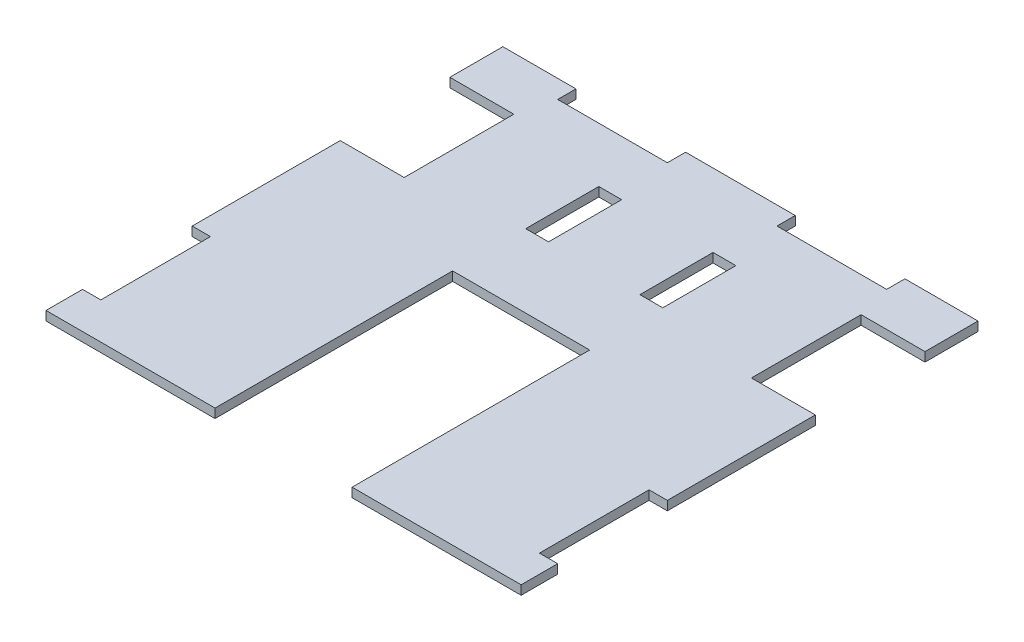
SolidWorks part; units mm, degrees
material "7050-T73510"
ref_plane "Front Plane" through (0, 0, 0) normal (0, 0, 1) x (1, 0, 0)
ref_plane "Top Plane" through (0, 0, 0) normal (0, 1, 0) x (1, 0, 0)
ref_plane "Right Plane" through (0, 0, 0) normal (1, 0, 0) x (0, 0, -1)
sketch "Sketch1" plane through (0, 0, 0) normal (0, 1, 0) x (1, 0, 0)
  line L0 (0, -55) -> (0, 55) construction
  line L1 (-165.1, -76.2) -> (165.1, -76.2)
  line L2 (-165.1, -76.2) -> (-165.1, 76.2)
  line L3 (-165.1, 76.2) -> (165.1, 76.2)
  line L4 (165.1, -76.2) -> (165.1, 76.2)
  line L5 (-165.1, -76.2) -> (165.1, 76.2) construction
  line L6 (-165.1, 76.2) -> (165.1, -76.2) construction
  line L7 (-165.1, -76.2) -> (-31.75, -76.2)
  line L8 (-165.1, -76.2) -> (-165.1, -241.3)
  line L9 (-165.1, -241.3) -> (-31.75, -241.3)
  line L10 (-31.75, -76.2) -> (-31.75, -241.3)
  line L11 (31.75, -76.2) -> (31.75, -241.3)
  line L12 (165.1, -241.3) -> (31.75, -241.3)
  line L13 (165.1, -76.2) -> (165.1, -241.3)
  line L14 (165.1, -76.2) -> (31.75, -76.2)
  line L15 (-47.625, -76.2) -> (-47.625, -241.3)
  line L16 (47.625, -76.2) -> (47.625, -241.3)
  point P0 (0, 0)
  dimension "D1" = 330.2
  dimension "D2" = 152.4
  dimension "D3" = 317.5
  dimension "D4" = 63.5
  dimension "D5" = 15.875
extrude "Boss-Extrude1" add sketch "Sketch1" along normal blind 6.35 contours L15 L1 L8 L9 | L14 L16 L12 L13 | L1 L7 L14 L4 L3 L2 region at (0, 0, 0) region at (-106.3625, 0, 158.75) region at (106.3625, 0, 158.75)
sketch "Sketch2" plane through (0, 6.35, 0) normal (0, 1, 0) x (1, 0, 0)
  line L0 (165.1, -241.3) -> (165.1, 76.2) construction
  line L1 (165.1, 39.37) -> (120.65, 39.37)
  line L2 (165.1, 39.37) -> (165.1, -36.83)
  line L3 (165.1, -36.83) -> (120.65, -36.83)
  line L4 (120.65, 39.37) -> (120.65, -36.83)
  line L5 (-165.1, 76.2) -> (165.1, 76.2) construction
  line L6 (165.1, -139.7) -> (152.4, -139.7)
  line L7 (165.1, -139.7) -> (165.1, -215.9)
  line L8 (165.1, -215.9) -> (152.4, -215.9)
  line L9 (152.4, -139.7) -> (152.4, -215.9)
  line L10 (0, -55) -> (0, 55) construction
  line L11 (-165.1, -215.9) -> (-152.4, -215.9)
  line L12 (-152.4, -139.7) -> (-152.4, -215.9)
  line L13 (-165.1, -139.7) -> (-152.4, -139.7)
  line L14 (-165.1, -139.7) -> (-165.1, -215.9)
  line L15 (-165.1, -36.83) -> (-120.65, -36.83)
  line L16 (-120.65, 39.37) -> (-120.65, -36.83)
  line L17 (-165.1, 39.37) -> (-120.65, 39.37)
  line L18 (-165.1, 39.37) -> (-165.1, -36.83)
  line L19 (-114.3, 63.5) -> (-38.1, 63.5)
  line L20 (114.3, 76.2) -> (38.1, 76.2)
  line L21 (114.3, 76.2) -> (114.3, 63.5)
  line L22 (114.3, 63.5) -> (38.1, 63.5)
  line L23 (38.1, 76.2) -> (38.1, 63.5)
  line L24 (-38.1, 76.2) -> (-38.1, 63.5)
  line L25 (-114.3, 76.2) -> (-38.1, 76.2)
  line L26 (-114.3, 76.2) -> (-114.3, 63.5)
  dimension "D1" = 44.45
  dimension "D2" = 12.7
  dimension "D3" = 76.2
  dimension "D4" = 76.2
  dimension "D5" = 36.83
  dimension "D6" = 215.9
  dimension "D7" = 76.2
  dimension "D8" = 12.7
  dimension "D9" = 76.2
extrude "Cut-Extrude1" cut sketch "Sketch2" against normal through all
sketch "Sketch3" plane through (0, 6.35, 0) normal (0, 1, 0) x (1, 0, 0)
  line L0 (-47.625, -76.2) -> (47.625, -76.2) construction
  line L1 (-47.625, -25.4) -> (-31.75, -25.4)
  line L2 (-47.625, -25.4) -> (-47.625, 25.4)
  line L3 (-47.625, 25.4) -> (-31.75, 25.4)
  line L4 (-31.75, -25.4) -> (-31.75, 25.4)
  line L5 (0, -55) -> (0, 55) construction
  line L6 (47.625, 25.4) -> (31.75, 25.4)
  line L7 (31.75, -25.4) -> (31.75, 25.4)
  line L8 (47.625, -25.4) -> (31.75, -25.4)
  line L9 (47.625, -25.4) -> (47.625, 25.4)
  dimension "D1" = 50.8
  dimension "D2" = 15.875
  dimension "D3" = 50.8
  dimension "D4" = 63.5
extrude "Cut-Extrude2" cut sketch "Sketch3" against normal through all
